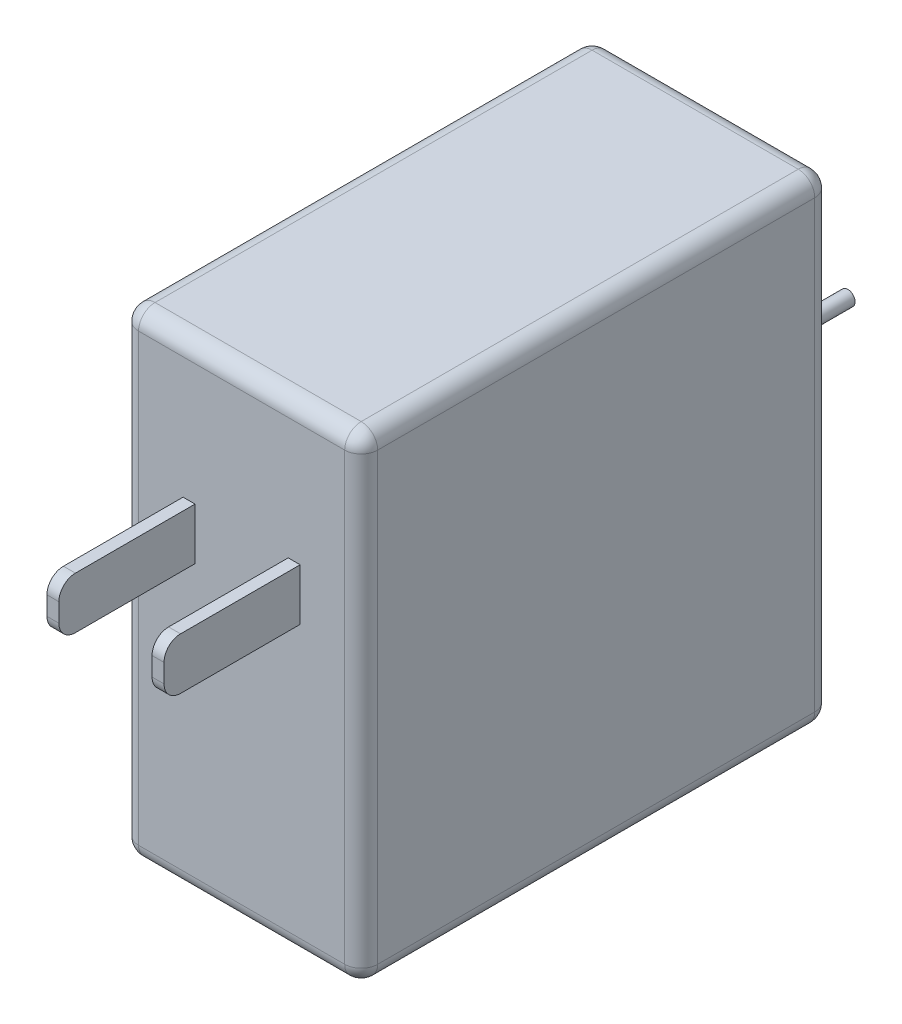
SolidWorks part; units mm, degrees
ref_plane "Front Plane" through (0, 0, 0) normal (0, 0, 1) x (1, 0, 0)
ref_plane "Top Plane" through (0, 0, 0) normal (0, 1, 0) x (1, 0, 0)
ref_plane "Right Plane" through (0, 0, 0) normal (1, 0, 0) x (0, 0, -1)
sketch "Sketch1" plane through (0, 0, 0) normal (0, 0, 1) x (1, 0, 0)
  line L5 (0, 29) -> (0, 6) construction
  line L6 (-14.5, 29) -> (14.5, 29)
  line L10 (-7.1, 12.26) -> (-7.1, 6)
  line L11 (7.1, 12.26) -> (5.65, 12.26)
  line L12 (-7.1, 12.26) -> (-5.65, 12.26)
  line L13 (7.1, 12.26) -> (7.1, 6)
  line L14 (5.65, 12.26) -> (5.65, 6)
  line L15 (7.1, 6) -> (5.65, 6)
  line L16 (-7.1, 6) -> (-5.65, 6)
  line L17 (-5.65, 12.26) -> (-5.65, 6)
  line L18 (-5.65, 6) -> (5.65, 6)
  line L19 (-14.5, 29) -> (-14.5, -29)
  line L20 (-14.5, -29) -> (14.5, -29)
  line L21 (14.5, 29) -> (14.5, -29)
  line L22 (-14.5, 29) -> (14.5, -29) construction
  line L23 (-14.5, -29) -> (14.5, 29) construction
  line L24 (0, 6) -> (0, 2.6928) construction
  point P0 (0, 0)
  dimension "D1" = 6.26
  dimension "D2" = 58
  dimension "D3" = 29
  dimension "D4" = 23
  dimension "D5" = 11.3
extrude "Boss-Extrude1" add sketch "Sketch1" against normal blind 57 contours L21 L6 L19 L20 L12 L17 L14 L11 L13 L15 L16 L10 | L15 L13 L11 L14 | L17 L12 L10 L16 region at (0, -0.0996, 0) region at (-6.375, 9.13, 0) region at (6.375, 9.13, 0)
extrude "Boss-Extrude2" add sketch "Sketch1<3>" along normal blind 16.51 contours L17 L12 L10 L16 | L15 L13 L11 L14 region at (-6.375, 9.13, 0) region at (6.375, 9.13, 0)
sketch "Sketch1<3>" plane through (0, 0, 0) normal (0, 0, 1) x (1, 0, 0) same geometry as "Sketch1"
fillet "Fillet1" radius 2 16 edges at (-14.5, 29, -28.5) (0, 29, -57) (14.5, 29, -28.5) (0, 29, 0) (-6.375, 12.26, 16.51) (-6.375, 6, 16.51) (6.375, 6, 16.51) (6.375, 12.26, 16.51) (0, -29, 0) (-14.5, 0, 0) (-14.5, 0, -57) (-14.5, -29, -28.5) (0, -29, -57) (14.5, -29, -28.5) (14.5, 0, -57) (14.5, 0, 0)
sketch "Sketch2" plane through (0, 0, -57) normal (0, 0, -1) x (-1, 0, 0)
  circle A0 centre (0, 0) radius 1.8885
  circle A1 centre (0, 0) radius 0.8821
extrude "Boss-Extrude3" add sketch "Sketch2" along normal blind 16.51 contours A1 region at (0, 0, -57)
extrude "Boss-Extrude4" add sketch "Sketch2<3>" along normal blind 8
sketch "Sketch2<3>" plane through (0, 0, -57) normal (0, 0, -1) x (-1, 0, 0) same geometry as "Sketch2"
fillet "Fillet2" radius 1 1 edges at (-1.8885, 0, -65)
